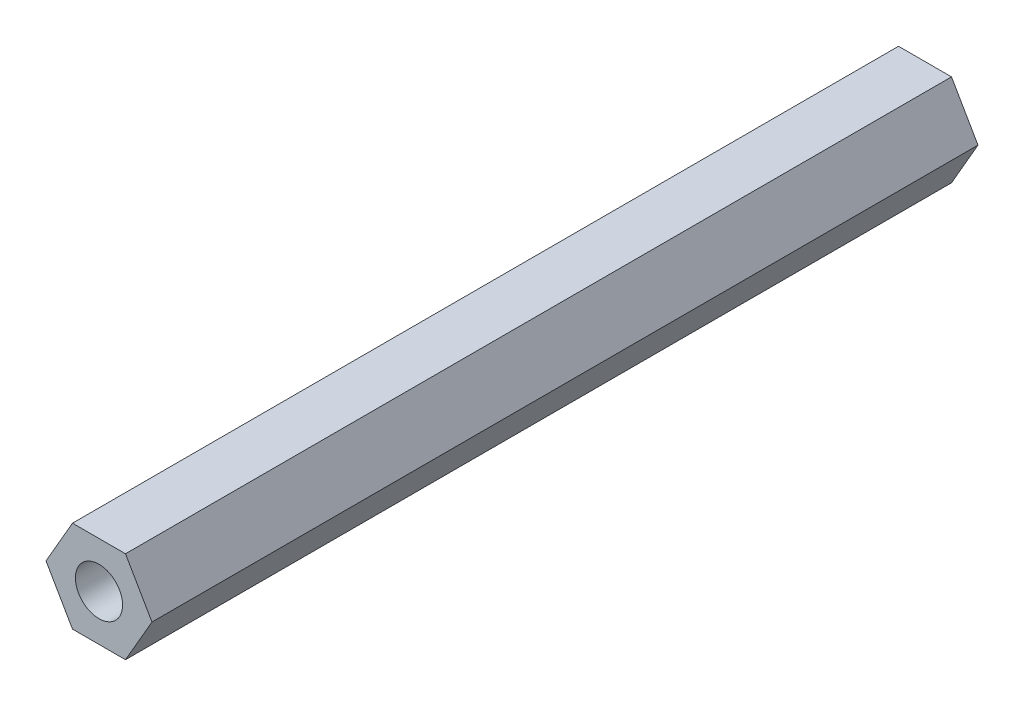
SolidWorks part; units mm, degrees
material "6061-T6 (SS)"
ref_plane "Front Plane" through (0, 0, 0) normal (0, 0, 1) x (1, 0, 0)
ref_plane "Top Plane" through (0, 0, 0) normal (0, 1, 0) x (1, 0, 0)
ref_plane "Right Plane" through (0, 0, 0) normal (1, 0, 0) x (0, 0, -1)
sketch "Sketch1" plane through (0, 0, 0) normal (0, 0, 1) x (1, 0, 0)
  line L1 (-3.6662, 6.35) -> (-7.3323, 0)
  line L2 (-7.3323, 0) -> (-3.6662, -6.35)
  line L3 (-3.6662, -6.35) -> (3.6662, -6.35)
  line L4 (3.6662, -6.35) -> (7.3323, 0)
  line L5 (7.3323, 0) -> (3.6662, 6.35)
  line L6 (3.6662, 6.35) -> (-3.6662, 6.35)
  circle A1 centre (0, 0) radius 3.2639
  circle A2 centre (0, 0) radius 6.35 construction
  dimension "D1" = 6.5278
  dimension "D2" = 12.7
extrude "Boss-Extrude1" add sketch "Sketch1" along normal blind 114.3
